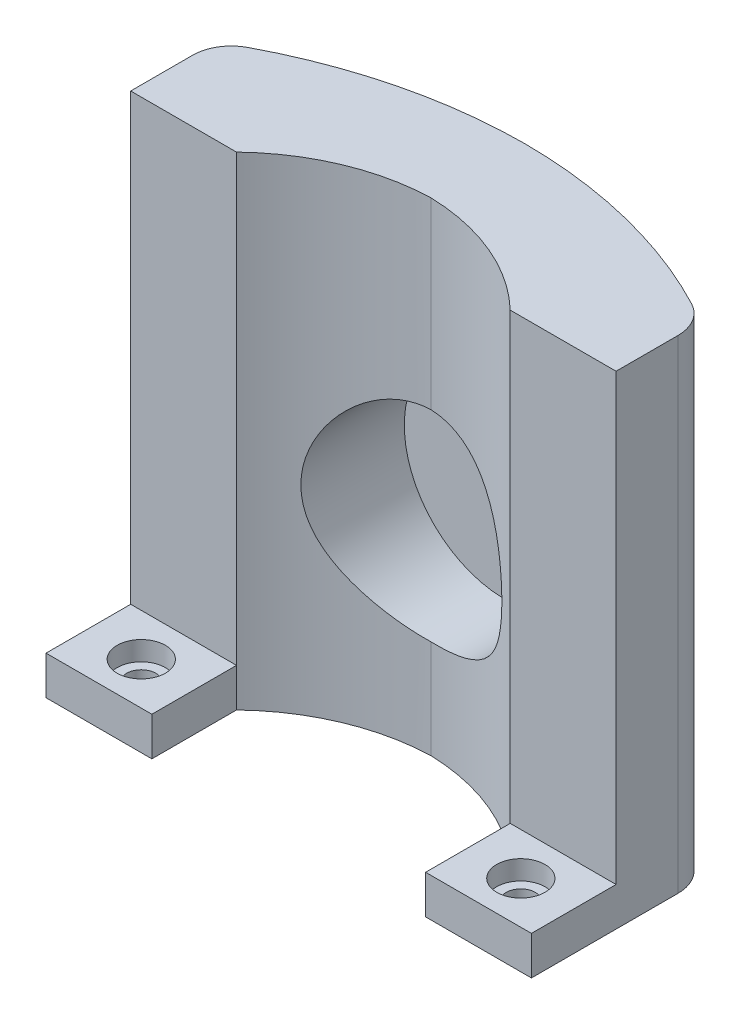
SolidWorks part; units mm, degrees
ref_plane "Front Plane" through (0, 0, 0) normal (0, 0, 1) x (1, 0, 0)
ref_plane "Top Plane" through (0, 0, 0) normal (0, 1, 0) x (1, 0, 0)
ref_plane "Right Plane" through (0, 0, 0) normal (1, 0, 0) x (0, 0, -1)
sketch "Sketch1" plane through (0, 0, 0) normal (0, 1, 0) x (1, 0, 0)
  line L0 (0, 83.6047) -> (0, -83.4001) construction
  line L1 (111.0333, 0.1023) -> (-95.2667, 0.1023) construction
  line L2 (-31.8963, 54.5068) -> (-31.8963, 32.258)
  line L3 (-31.8963, 32.258) -> (-17.9866, 32.258)
  line L4 (-17.9866, 32.258) -> (-17.9866, 43.3824)
  line L5 (31.8963, 54.5068) -> (31.8963, 32.258)
  line L6 (31.8963, 32.258) -> (17.9866, 32.258)
  line L7 (17.9866, 32.258) -> (17.9866, 43.3824)
  line L8 (-17.9866, 43.3824) -> (-31.8963, 43.3824)
  line L9 (17.9866, 43.3824) -> (31.8963, 43.3824)
  circle A0 centre (0, 0) radius 66.04
  circle A1 centre (0, 32.258) radius 15.9195
  arc A2 (-17.9866, 43.3824) -> (0, 50.9549) centre (0.8012, 23.9042) cw
  arc A3 (0, 63.2878) -> (-31.8963, 54.5068) centre (0.1805, 0.3111) ccw
  arc A4 (17.9866, 43.3824) -> (0, 50.9549) centre (-0.8012, 23.9042) ccw
  arc A5 (0, 63.2878) -> (31.8963, 54.5068) centre (-0.1805, 0.3111) cw
  dimension "D1" = 132.08
  dimension "D2" = 31.8389
  dimension "D3" = 32.258
extrude "Boss-Extrude2" add sketch "Sketch1" along normal blind 63.5 contours A5 A3 L2 L8 A2 A4 L9 L5 region at (0, 0, -53.2622)
extrude "Boss-Extrude3" add sketch "Sketch1<4>" along normal blind 5.08 contours L4 L8 L2 L3 | L9 L7 L6 L5 region at (-24.9415, 0, -37.8202) region at (24.9415, 0, -37.8202)
sketch "Sketch1<4>" plane through (0, 0, 0) normal (0, 1, 0) x (1, 0, 0) same geometry as "Sketch1"
sketch "Sketch2" plane through (0, 5.08, 0) normal (0, 1, 0) x (1, 0, 0)
  line L0 (0, 68.0963) -> (0, 18.7701) construction
  circle A0 centre (-24.9415, 37.8202) radius 3.175
  circle A1 centre (24.9415, 37.8202) radius 3.175
  dimension "D1" = 6.35
extrude "Cut-Extrude1" cut sketch "Sketch2" against normal blind 2.54
sketch "Sketch3" plane through (0, 2.54, 0) normal (0, 1, 0) x (1, 0, 0)
  line L0 (0, 65.8395) -> (0, 41.2689) construction
  circle A0 centre (-24.9415, 37.8202) radius 1.905
  circle A1 centre (24.9415, 37.8202) radius 1.905
  dimension "D1" = 3.81
extrude "Cut-Extrude2" cut sketch "Sketch3" against normal through all
sketch "Sketch4" plane through (0, 0, 0) normal (0, 0, 1) x (1, 0, 0)
  line L0 (0, -3.8969) -> (0, 35.2858) construction
  line L1 (-33.3733, 63.5) -> (33.5775, 63.5) construction
  line L2 (-35.0053, 12.7) -> (38.3963, 12.7) construction
  circle A0 centre (0, 26.1755) radius 13.208
  dimension "D2" = 26.416
  dimension "D1" = 12.7
extrude "Cut-Extrude3" cut sketch "Sketch4" against normal blind 17.272 from surface starting at face at (-24.9415, 34.29, -43.3824)
fillet "Fillet1" radius 5.08 2 edges at (31.8963, 31.75, -54.5068) (-31.8963, 31.75, -54.5068)
